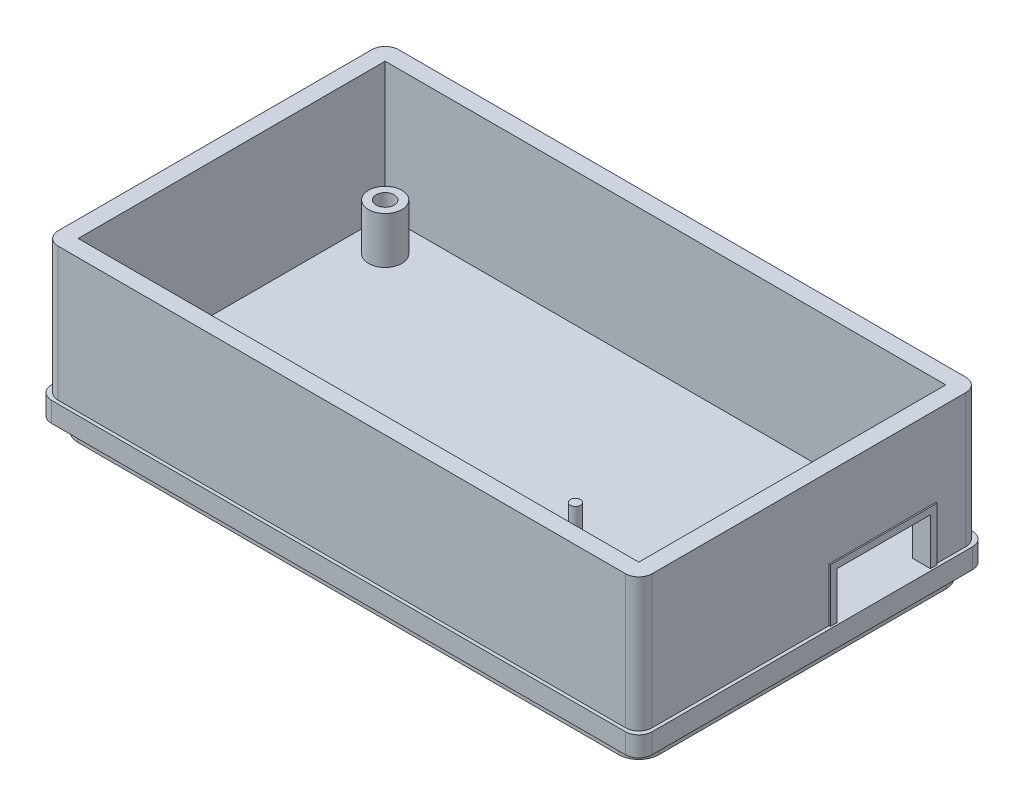
SolidWorks part; units mm, degrees
ref_plane "Front Plane" through (0, 0, 0) normal (0, 0, 1) x (1, 0, 0)
ref_plane "Top Plane" through (0, 0, 0) normal (0, 1, 0) x (1, 0, 0)
ref_plane "Right Plane" through (0, 0, 0) normal (1, 0, 0) x (0, 0, -1)
sketch "Sketch1" plane through (0, 0, 0) normal (0, 1, 0) x (1, 0, 0)
  line L1 (-45, 26) -> (45, 26)
  line L2 (-45, 26) -> (-45, -26)
  line L3 (-45, -26) -> (45, -26)
  line L4 (45, 26) -> (45, -26)
  dimension "D1" = 52
  dimension "D2" = 90
  dimension "D3" = 45
  dimension "D4" = 26
extrude "Boss-Extrude1" add sketch "Sketch1" along normal blind 3
sketch "Sketch3" plane through (0, 0, 0) normal (0, 1, 0) x (1, 0, 0)
  line L1 (-41.5, 22.5) -> (41.5, 22.5)
  line L2 (-41.5, 22.5) -> (-41.5, -22.5)
  line L3 (-41.5, -22.5) -> (41.5, -22.5)
  line L4 (41.5, 22.5) -> (41.5, -22.5)
  dimension "D1" = 45
  dimension "D2" = 83
  dimension "D3" = 41.5
  dimension "D4" = 22.5
sketch "Sketch4" plane through (0, 0, 0) normal (0, 1, 0) x (1, 0, 0)
  line L2 (-41.5, -22.5) -> (41.5, -22.5) construction
  line L3 (-41.5, 22.5) -> (-41.5, -22.5) construction
  circle A1 centre (29, -19.5) radius 2.5
  circle A2 centre (-37, 18) radius 2.5
  circle A3 centre (-37, -16.5) radius 2.5
  dimension "D4" = 5
  dimension "D5" = 3
  dimension "D8" = 4.5
  dimension "D9" = 6
extrude "Boss-Extrude2" add sketch "Sketch4" along normal blind 7 from surface starting at face at (0, 3, 0)
sketch "Sketch5" plane through (0, 0, 0) normal (0, 1, 0) x (1, 0, 0)
  circle A0 centre (-37, 18) radius 1.35
  circle A1 centre (-37, -16.5) radius 1.35
extrude "Cut-Extrude2" cut sketch "Sketch5" against normal through all both and the other way through all from surface starting at face at (-37, 10, -15.5)
sketch "Sketch6" plane through (0, 0, 0) normal (0, 1, 0) x (1, 0, 0)
  circle A0 centre (29, -19.5) radius 0.75
  dimension "D1" = 1.5
extrude "Boss-Extrude3" add sketch "Sketch6" along normal blind 12.5 from surface starting at face at (29, 10, 22)
sketch "Sketch7" plane through (0, 0, 0) normal (0, 1, 0) x (1, 0, 0)
  line L4 (40.5, 21.5) -> (-40.5, 21.5)
  line L5 (-40.5, 21.5) -> (-40.5, -21.5)
  line L6 (-40.5, -21.5) -> (40.5, -21.5)
  line L7 (40.5, -21.5) -> (40.5, 21.5)
  line L8 (43.5, 24.5) -> (-43.5, 24.5)
  line L9 (43.5, -24.5) -> (43.5, 24.5)
  line L10 (-43.5, -24.5) -> (43.5, -24.5)
  line L11 (-43.5, 24.5) -> (-43.5, -24.5)
  line L12 (43.5, 24.5) -> (-43.5, 24.5)
  line L13 (43.5, -24.5) -> (43.5, 24.5)
  line L14 (-43.5, -24.5) -> (43.5, -24.5)
  line L15 (-43.5, 24.5) -> (-43.5, -24.5)
  dimension "D1" = 2
  dimension "D2" = 3
extrude "Boss-Extrude4" add sketch "Sketch7" against normal blind 2
fillet "Fillet1" radius 3 4 edges at (-43.5, -1, 24.5) (-43.5, -1, -24.5) (43.5, -1, 24.5) (43.5, -1, -24.5)
sketch "Sketch8" plane through (0, 0, 0) normal (0, 1, 0) x (1, 0, 0)
  line L4 (44.5, 25.5) -> (-44.5, 25.5)
  line L5 (-44.5, 25.5) -> (-44.5, -25.5)
  line L6 (-44.5, -25.5) -> (44.5, -25.5)
  line L7 (44.5, -25.5) -> (44.5, 25.5)
  line L8 (42, 23) -> (-42, 23)
  line L9 (42, -23) -> (42, 23)
  line L10 (-42, -23) -> (42, -23)
  line L11 (-42, 23) -> (-42, -23)
  line L12 (42, 23) -> (-42, 23)
  line L13 (42, -23) -> (42, 23)
  line L14 (-42, -23) -> (42, -23)
  line L15 (-42, 23) -> (-42, -23)
  dimension "D1" = 0.5
  dimension "D2" = 2.5
extrude "Boss-Extrude8" add sketch "Sketch8" along normal blind 20 from surface starting at face at (29, 3, 22)
fillet "Fillet2" radius 2 8 edges at (-45, 1.5, 26) (-44.5, 13, 25.5) (-45, 1.5, -26) (-44.5, 13, -25.5) (45, 1.5, -26) (45, 1.5, 26) (44.5, 13, -25.5) (44.5, 13, 25.5)
sketch "Sketch9" plane through (0, 0, 0) normal (1, 0, 0) x (0, 0, -1)
  line L1 (4, 10) -> (18, 10)
  line L2 (4, 10) -> (4, 3)
  line L3 (4, 3) -> (18, 3)
  line L4 (18, 10) -> (18, 3)
  dimension "D1" = 14
  dimension "D2" = 7
  dimension "D4" = 5.5
extrude "Cut-Extrude3" cut sketch "Sketch9" along normal blind 15 from surface starting at face at (42, 13, 0)
sketch "Sketch10" plane through (0, 0, 0) normal (1, 0, 0) x (0, 0, -1)
  line L9 (18, 3) -> (18, 10)
  line L15 (18, 10) -> (4, 10)
  line L16 (4, 10) -> (4, 3)
  line L17 (19, 3) -> (19, 11)
  line L22 (3, 11) -> (3, 3)
  line L23 (19, 11) -> (3, 11)
  line L24 (19, 3) -> (19, 11)
  line L25 (3, 11) -> (3, 3)
  line L26 (19, 11) -> (3, 11)
  line L27 (3, 3) -> (4, 3)
  line L28 (18, 3) -> (19, 3)
  dimension "D2" = 1
  dimension "D1" = 1
extrude "Boss-Extrude9" add sketch "Sketch10" along normal blind 0.2 from surface starting at face at (44.5, 9.75, -5.5)
